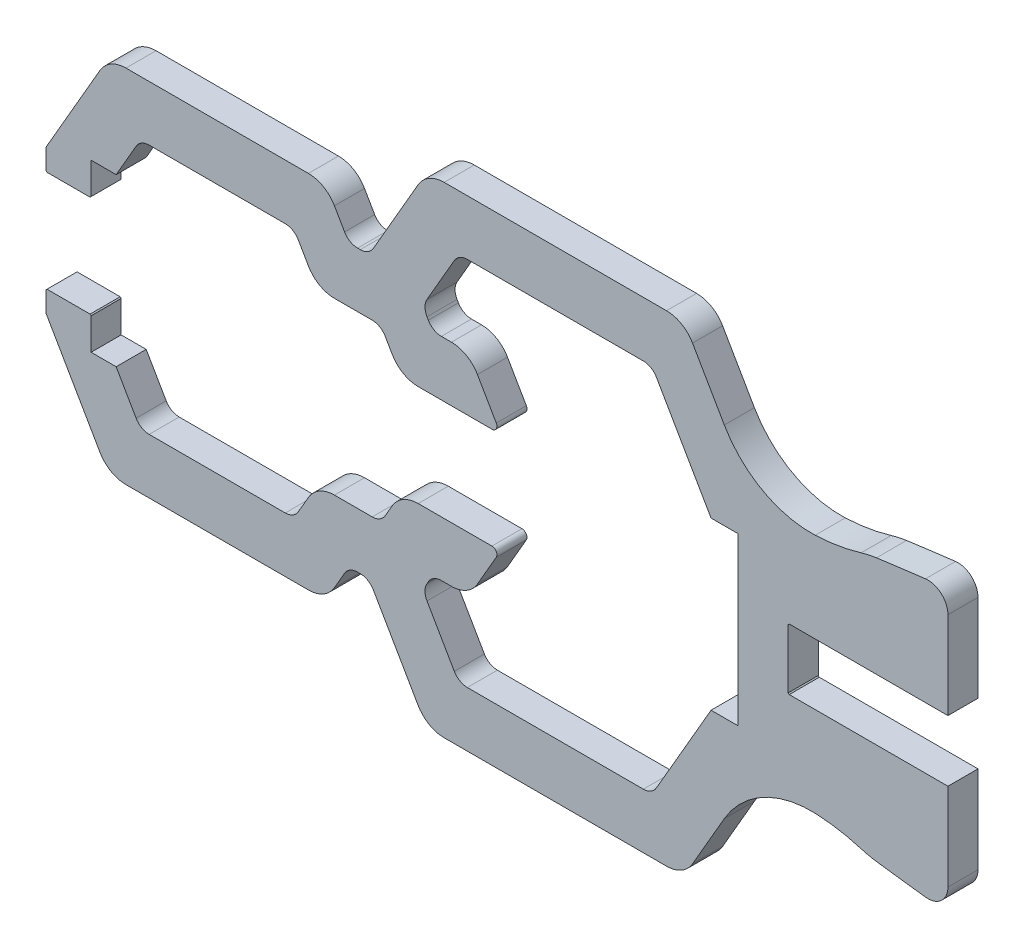
SolidWorks part; units mm, degrees
ref_plane "前视基准面" through (0, 0, 0) normal (0, 0, 1) x (1, 0, 0)
ref_plane "上视基准面" through (0, 0, 0) normal (0, 1, 0) x (1, 0, 0)
ref_plane "右视基准面" through (0, 0, 0) normal (1, 0, 0) x (0, 0, -1)
ref_axis "基准轴1" through (-271.0774, 0, 0) along (1, 0, 0)
sketch "草图1" plane through (0, 0, 0) normal (0, 0, 1) x (1, 0, 0)
  line L0 (-19.6441, 0) -> (19.6441, 0) construction
  line L1 (9, 65) -> (3.5939, 47)
  line L2 (3.5939, 47) -> (12.8315, 31)
  line L3 (12.8315, 31) -> (-1.2116, 31)
  line L4 (-1.2116, 31) -> (-3.4641, 23.5)
  line L5 (-7.7942, 31) -> (0, 17.5)
  line L6 (80, -11.5) -> (380, -7.1666)
  line L7 (0, -17.5) -> (24, -17)
  line L9 (-1.2116, -31) -> (-3.4641, -23.5)
  line L10 (12.8315, -31) -> (-1.2116, -31)
  line L11 (3.5939, -47) -> (12.8315, -31)
  line L12 (9, -65) -> (3.5939, -47)
  line L13 (9, 65) -> (3, 65)
  line L14 (3, 65) -> (-7.3923, 47)
  line L15 (-7.3923, 47) -> (-26.859, 35.7609)
  line L16 (-26.859, 35.7609) -> (-40, 13)
  line L17 (-26.859, -35.7609) -> (-40, -13)
  line L18 (-7.3923, -47) -> (-26.859, -35.7609)
  line L19 (3, -65) -> (-7.3923, -47)
  line L20 (9, -65) -> (3, -65)
  line L21 (-95, 16) -> (-95, -16) construction
  line L22 (-150, 13) -> (-156.3509, 24)
  line L23 (-156.3509, 24) -> (-182, 24)
  line L24 (-150, -13) -> (-156.3509, -24)
  line L25 (-156.3509, -24) -> (-182, -24)
  line L26 (-182, 24) -> (-187.7735, 14)
  line L27 (-187.7735, 14) -> (-189.7735, 14)
  line L28 (-189.7735, 14) -> (-192.0829, 18)
  line L29 (-192.0829, 18) -> (-213.7506, 18)
  line L30 (-213.7506, 18) -> (-220, 7.1756)
  line L31 (-213.7506, -18) -> (-220, -7.1756)
  line L32 (-192.0829, -18) -> (-213.7506, -18)
  line L33 (-189.7735, -14) -> (-192.0829, -18)
  line L34 (-187.7735, -14) -> (-189.7735, -14)
  line L35 (-182, -24) -> (-187.7735, -14)
  line L36 (0, 17.5) -> (0, -17.5) construction
  line L37 (0, 17.5) -> (24, 17)
  line L38 (80, 11.5) -> (380, 7.1666)
  line L39 (680, 5) -> (780, 5)
  line L40 (680, -5) -> (780, -5)
  line L41 (780, 5) -> (780, -5)
  line L42 (3.0165, 36) -> (-1.3488, 43.561)
  line L43 (-1.3488, 43.561) -> (-14.4449, 36)
  line L44 (-14.4449, 36) -> (3.0165, 36)
  line L45 (-1.3488, -43.561) -> (-14.4449, -36)
  line L46 (3.0165, -36) -> (-1.3488, -43.561)
  line L47 (-14.4449, -36) -> (3.0165, -36)
  line L48 (-7.7942, 31) -> (-29.6077, 31)
  line L49 (-7.7942, -31) -> (-29.6077, -31)
  line L50 (-7.7942, -31) -> (0, -17.5)
  line L53 (-195.2583, -12.5) -> (-210.5751, -12.5)
  line L62 (-210.5751, -12.5) -> (-213, -8.3)
  line L77 (-195.2583, 12.5) -> (-210.5751, 12.5)
  line L80 (-210.5751, 12.5) -> (-213, 8.3)
  line L108 (-182.4145, -12.2821) -> (-178.8246, -18.5)
  line L109 (-178.8246, -18.5) -> (-159.5263, -18.5)
  line L110 (-159.5263, -18.5) -> (-153.6373, -8.3)
  line L111 (-153.6373, -8.3) -> (-153.6373, 8.3) construction
  line L115 (-182.4145, 12.2821) -> (-178.8246, 18.5)
  line L116 (-178.8246, 18.5) -> (-159.5263, 18.5)
  line L117 (-159.5263, 18.5) -> (-153.6373, 8.3)
  line L118 (-184.5899, -5.05) -> (-186.5818, -8.5)
  line L119 (-186.5818, -8.5) -> (-192.9489, -8.5)
  line L120 (-192.9489, -8.5) -> (-195.2583, -12.5)
  line L123 (-192.9489, 8.5) -> (-195.2583, 12.5)
  line L124 (-182.4145, -12.2821) -> (-181.4145, -10.55)
  line L125 (-181.4145, -10.55) -> (-177.8127, -10.55)
  line L126 (-177.8127, -10.55) -> (-174.6373, -5.05)
  line L127 (-174.6373, -5.05) -> (-184.5899, -5.05)
  line L128 (-186.5818, 8.5) -> (-192.9489, 8.5)
  line L129 (-177.8127, 10.55) -> (-174.6373, 5.05)
  line L130 (-174.6373, 5.05) -> (-184.5899, 5.05)
  line L131 (-184.5899, 5.05) -> (-186.5818, 8.5)
  line L132 (-182.4145, 12.2821) -> (-181.4145, 10.55)
  line L133 (-181.4145, 10.55) -> (-177.8127, 10.55)
  line L135 (-220, 7.1756) -> (-220, 5.05)
  line L136 (-213, 8.3) -> (-215.5, 8.3)
  line L137 (-215.5, 8.3) -> (-215.5, 5.05)
  line L138 (-215.5, 5.05) -> (-220, 5.05)
  line L139 (-215.5, -5.05) -> (-220, -5.05)
  line L140 (-215.5, -8.3) -> (-215.5, -5.05)
  line L141 (-213, -8.3) -> (-215.5, -8.3)
  line L142 (-150.9373, 3.05) -> (-150.9373, -3.05)
  line L143 (-145.9373, 3.05) -> (-145.9373, -3.05)
  line L144 (-220, 5.05) -> (-220, 0) construction
  line L145 (-220, -5.05) -> (-220, -7.1756)
  line L146 (-150.9373, 3.05) -> (-145.9373, 3.05) construction
  line L147 (-220, 0) -> (-220, -5.05) construction
  line L148 (-145.9373, -3.05) -> (-150.9373, -3.05) construction
  line L151 (-130, -14.0157) -> (-130, -3.05)
  line L152 (-130, -3.05) -> (-145.9373, -3.05)
  line L154 (-145.9373, 3.05) -> (-130, 3.05)
  line L155 (-130, -3.05) -> (-130, 0) construction
  line L156 (-130, 3.05) -> (-130, 14.0157)
  line L157 (-130, 0) -> (-130, 3.05) construction
  line L158 (-153.6373, -8.3) -> (-150.9373, -8.3)
  line L159 (-150.9373, -8.3) -> (-150.9373, -3.05)
  line L160 (-153.6373, 8.3) -> (-150.9373, 8.3)
  line L161 (-150.9373, 8.3) -> (-150.9373, 3.05)
  arc A0 (-40, 13) -> (-52, 13) centre (-46, 30.5) cw
  arc A1 (-40, -13) -> (-52, -13) centre (-46, -30.5) ccw
  arc A2 (-52, 13) -> (-138, 13) centre (-95, -293.6667) ccw
  arc A3 (-52, -13) -> (-138, -13) centre (-95, 293.6667) cw
  arc A4 (-150, -13) -> (-138, -13) centre (-144, -30.5) cw
  arc A5 (-150, 13) -> (-138, 13) centre (-144, 30.5) ccw
  arc A6 (24, 17) -> (36, 14) centre (40.2074, 56.3296) ccw
  arc A7 (36, 14) -> (80, 11.5) centre (87.5238, 532.3687) ccw
  arc A8 (36, -14) -> (80, -11.5) centre (87.5238, -532.3687) cw
  arc A9 (24, -17) -> (36, -14) centre (40.2074, -56.3296) cw
  arc A10 (380, 7.1666) -> (680, 5) centre (680, 20776.0363) ccw
  arc A11 (380, -7.1666) -> (680, -5) centre (680, -20776.0363) cw
  point P30 (-46, 12)
  point P31 (-46, -12)
  dimension "D4" = 24
  dimension "D5" = 24
  dimension "D15" = 34
  dimension "D17" = 16.6
  dimension "D1" = 130
  dimension "D2" = 35
  dimension "D3" = 120
  dimension "D6" = 220
  dimension "D7" = 40
  dimension "D8" = 150
  dimension "D9" = 36
  dimension "D10" = 32
  dimension "D11" = 48
  dimension "D12" = 120
  dimension "D13" = 12
  dimension "D14" = 120
  dimension "D16" = 26
  dimension "D18" = 100
  dimension "D19" = 10
  dimension "D20" = 23
  dimension "D21" = 28
  dimension "D22" = 80
  dimension "D23" = 12
  dimension "D24" = 300
  dimension "D25" = 2
  dimension "D26" = 28
  dimension "D27" = 7
  dimension "D28" = 34
  dimension "D29" = 30
  dimension "D30" = 18
  dimension "D31" = 30
  dimension "D32" = 9
  dimension "D33" = 7.5
  dimension "D34" = 6
  dimension "D35" = 6
  dimension "D36" = 6
  dimension "D37" = 5
  dimension "D38" = 5.5
  dimension "D39" = 5.5
  dimension "D40" = 5.5
  dimension "D41" = 5.5
  dimension "D42" = 5.5
  dimension "D43" = 5.5
  dimension "D44" = 5.5
  dimension "D45" = 5.5
  dimension "D46" = 10.1
  dimension "D47" = 2
  dimension "D48" = 5.5
  dimension "D49" = 5
  dimension "D50" = 38
  dimension "D51" = 10.1
  dimension "D52" = 4.5
  dimension "D53" = 1000
  dimension "D54" = 6.1
  dimension "D55" = 16.6
  dimension "D56" = 90
  dimension "D57" = 21
  dimension "D59" = 2.7
extrude "凸台-拉伸1" add sketch "草图1" along normal mid plane 3 contours A5 L22 L23 L26 L27 L28 L29 L30 L135 L138 L137 L136 L80 L77 L123 L128 L131 L130 L129 L133 L132 L115 L116 L117 L111 L110 L109 L108 L124 L125 L126 L127 L118 L119 L120 L53 L62 L141 L140 L139 L145 L31 L32 L33 L34 L35 L25 region at (-131.02, 8.5329, 0)
fillet "圆角4" radius 10 4 edges at (-138, -13, 0) (-138, 13, 0) (-150, 13, 0) (-150, -13, 0)
fillet "圆角7" radius 1.5 18 edges at (-210.5751, 12.5, 0) (-210.5751, -12.5, 0) (-195.2583, -12.5, 0) (-186.5818, 8.5, 0) (-195.2583, 12.5, 0) (-178.8246, 18.5, 0) (-159.5263, 18.5, 0) (-159.5263, -18.5, 0) (-178.8246, -18.5, 0) (-186.5818, -8.5, 0) (-182.4145, 12.2821, 0) (-181.4145, 10.55, 0) (-181.4145, -10.55, 0) (-182.4145, -12.2821, 0) (-189.7735, -14, 0) (-187.7735, -14, 0) (-187.7735, 14, 0) (-189.7735, 14, 0)
fillet "圆角8" radius 3 14 edges at (-213.7506, 18, 0) (-213.7506, -18, 0) (-192.0829, -18, 0) (-192.0829, 18, 0) (-177.8127, 10.55, 0) (-177.8127, -10.55, 0) (-184.5899, 5.05, 0) (-192.9489, 8.5, 0) (-192.9489, -8.5, 0) (-184.5899, -5.05, 0) (-182, 24, 0) (-156.3509, 24, 0) (-156.3509, -24, 0) (-182, -24, 0)
chamfer "倒角1" distance 0.1 angle 45 6 edges at (-145.9373, -3.05, 0) (-145.9373, 3.05, 0) (-220, -5.05, 0) (-215.5, -5.05, 0) (-220, 5.05, 0) (-215.5, 5.05, 0)
fillet "圆角9" radius 2 2 edges at (-130, -14.0157, 0) (-130, 14.0157, 0)
fillet "圆角10" radius 0.5 2 edges at (-174.6373, -5.05, 0) (-174.6373, 5.05, 0)
